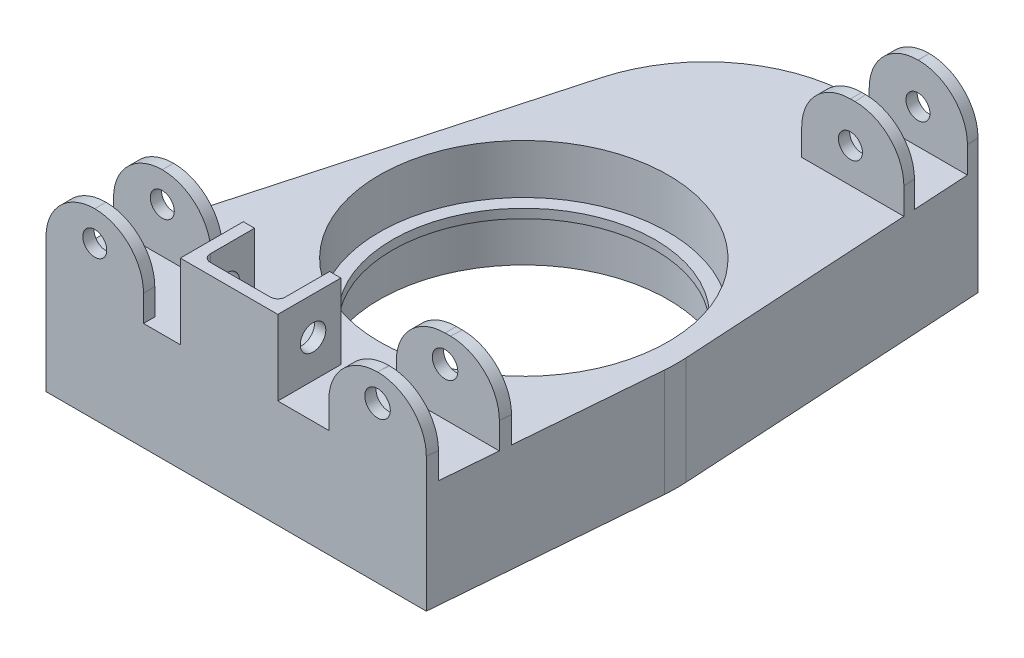
SolidWorks part; units mm, degrees
ref_plane "Front Plane" through (0, 0, 0) normal (0, 0, 1) x (1, 0, 0)
ref_plane "Top Plane" through (0, 0, 0) normal (0, 1, 0) x (1, 0, 0)
ref_plane "Right Plane" through (0, 0, 0) normal (1, 0, 0) x (0, 0, -1)
sketch "Sketch1" plane through (0, 0, 0) normal (0, 1, 0) x (1, 0, 0)
  line L0 (-78.3166, -83.4598) -> (50.4493, -83.4598)
  line L1 (56.8393, -5.2886) -> (50.4493, 103.3395)
  line L2 (50.4493, 103.3395) -> (9.0638, 103.3395)
  line L3 (-39.909, 66.0414) -> (-73.7736, -56.7898)
  line L4 (50.4493, 103.3395) -> (50.4493, -83.4598) construction
  line L5 (50.4493, -83.4598) -> (56.8393, -5.2886)
  line L6 (-78.3166, -83.4598) -> (-78.3166, -56.7898)
  line L7 (-78.3166, -56.7898) -> (-73.7736, -56.7898)
  circle A0 centre (0, 0) radius 48.895
  circle A2 centre (0, 0) radius 120.65
  arc A3 (9.0638, 103.3395) -> (-39.909, 66.0414) centre (9.0638, 52.5395) ccw
  point P10 (0, -48.895)
  point P11 (48.895, 0)
  point P16 (-48.895, 0)
  dimension "D2" = 97.79
  dimension "D3" = 7.62
  dimension "D4" = 8.89
  dimension "D5" = 26.67
  dimension "D1" = 241.3
  dimension "D6" = 50.8
extrude "Base" add sketch "Sketch1" along normal blind 36.5 contours L2 L3 L0 L1 A0 | L1 L4 A0 L5 region at (-76.0109, 0, 70.1248)
sketch "Sketch2" plane through (0, 36.5, 0) normal (0, 1, 0) x (1, 0, 0)
  line L0 (50.4493, 103.3395) -> (50.6734, 99.5295)
  line L1 (56.8393, -5.2886) -> (50.4493, 103.3395) construction
  line L2 (50.6734, 99.5295) -> (17.4293, 99.5295)
  line L3 (17.4293, 99.5295) -> (17.4293, 103.3395)
  line L4 (50.4493, 103.3395) -> (9.0638, 103.3395) construction
  line L5 (17.4293, 103.3395) -> (50.4493, 103.3395)
  line L6 (17.4293, -79.6498) -> (50.7608, -79.6498)
  line L7 (50.7608, -79.6498) -> (50.4493, -83.4598)
  line L8 (-78.3166, -83.4598) -> (50.4493, -83.4598) construction
  line L9 (50.4493, -83.4598) -> (17.4293, -83.4598)
  line L10 (17.4293, -83.4598) -> (17.4293, -79.6498)
  line L11 (17.4293, 103.3395) -> (17.4293, -83.4598) construction
  line L12 (50.4493, -83.4598) -> (56.8393, -5.2886) construction
  line L13 (17.4293, 80.4795) -> (17.4293, 76.6695)
  line L14 (17.4293, 76.6695) -> (52.0182, 76.6695)
  line L15 (52.0182, 76.6695) -> (51.794, 80.4795)
  line L16 (51.794, 80.4795) -> (17.4293, 80.4795)
  line L17 (-78.3166, -83.4598) -> (-78.3166, -56.7898) construction
  line L18 (17.4293, -56.7898) -> (52.6294, -56.7898)
  line L19 (17.4293, -56.7898) -> (17.4293, -60.5998)
  line L20 (17.4293, -60.5998) -> (52.318, -60.5998)
  line L21 (52.6294, -56.7898) -> (52.318, -60.5998)
  line L22 (-45.2966, -56.7898) -> (-78.3166, -56.7898)
  line L23 (-45.2966, -56.7898) -> (-45.2966, -60.5998)
  line L24 (-45.2966, -60.5998) -> (-78.3166, -60.5998)
  line L25 (-78.3166, -56.7898) -> (-78.3166, -60.5998)
  line L26 (-45.2966, -83.4598) -> (-45.2966, -60.0458) construction
  line L27 (-78.3166, -79.6498) -> (-45.2966, -79.6498)
  line L28 (-78.3166, -79.6498) -> (-78.3166, -83.4598)
  line L29 (-78.3166, -83.4598) -> (-45.2966, -83.4598)
  line L30 (-45.2966, -79.6498) -> (-45.2966, -83.4598)
  line L31 (-78.3166, -83.4598) -> (50.4493, -83.4598) construction
  point P40 (-78.3166, -83.4598)
  dimension "D1" = 33.02
  dimension "D2" = 3.81
  dimension "D3" = 3.81
  dimension "D4" = 19.05
  dimension "D5" = 3.81
  dimension "D6" = 3.81
  dimension "D7" = 19.05
  dimension "D8" = 33.02
  dimension "D9" = 3.81
  dimension "D10" = 3.81
extrude "A-Arms" add sketch "Sketch2" along normal blind 25.4
fillet "Fillet a-arm tab f" radius 16.51 12 edges at (50.605, 61.9, 81.5548) (52.4737, 61.9, 58.6948) (17.4293, 61.9, 81.5548) (17.4293, 61.9, 58.6948) (51.9061, 61.9, -78.5745) (50.5614, 61.9, -101.4345) (17.4293, 61.9, -78.5745) (17.4293, 61.9, -101.4345) (-78.3166, 61.9, 81.5548) (-45.2966, 61.9, 81.5548) (-45.2966, 61.9, 58.6948) (-78.3166, 61.9, 58.6948)
fillet "Fillet2" radius 50.8 1 edges at (56.8393, 18.25, 5.2886)
ref_plane "Plane1" through (0, 1, 0) normal (0, -1, 0) x (-1, 0, 0)
sketch "Sketch3" plane through (0, 1, 0) normal (0, -1, 0) x (-1, 0, 0)
  line L0 (43.8545, 51.7309) -> (51.7371, 53.9041)
  line L1 (39.909, 66.0414) -> (73.7736, -56.7898) construction
  line L2 (63.9719, -21.2377) -> (72.1885, -18.9724)
  line L3 (54.0145, 33.5988) -> (63.3923, -0.4157)
  line L4 (43.8545, 51.7309) -> (63.9719, -21.2377)
  circle A0 centre (0, 0) radius 71.12
  circle A1 centre (53.7624, 46.5582) radius 4.191
  circle A2 centre (70.1632, -11.6265) radius 4.191
  arc A3 (56.852, 39.5926) -> (51.7371, 53.9041) centre (53.7624, 46.5582) ccw
  arc A4 (72.1885, -18.9724) -> (69.039, -4.0899) centre (70.1632, -11.6265) ccw
  arc A5 (63.3923, -0.4157) -> (69.039, -4.0899) centre (68.2896, 0.9345) ccw
  arc A6 (54.0145, 33.5988) -> (56.852, 39.5926) centre (58.9118, 34.949) cw
  dimension "D1" = 60.452
  dimension "D2" = 142.24
  dimension "D3" = 8.382
  dimension "D4" = 8.382
  dimension "D5" = 15.24
  dimension "D6" = 15.24
  dimension "D7" = 5.08
extrude "Boss-Extrude3" add sketch "Sketch3" against normal blind 10 contours L3 A6 A3 A0 A1 L0 L4 L2 A2 A4 A5 | A0 A3 L0 A1 | L2 A4 A0 A2 region at (-57.0001, 1, -15.6865) region at (-49.7533, 1, -53.1565) region at (-69.0083, 1, 17.9571)
fillet "Fillet3" radius 12.7 2 edges at (-43.8545, 6, -51.7309) (-63.9719, 6, 21.2377)
sketch "Sketch6" plane through (0, 0, -103.3395) normal (0, 0, -1) x (-1, 0, 0)
  line L0 (-33.9251, 61.9) -> (-33.9251, 40.2979) construction
  circle A1 centre (-33.9251, 48.2) radius 4.064
  dimension "D1" = 13.7
  dimension "D2" = 8.128
extrude "Tab Holes 1" cut sketch "Sketch6" against normal blind 38.1
sketch "Sketch7" plane through (0, 0, 56.7898) normal (0, 0, -1) x (-1, 0, 0)
  line L0 (61.8066, 61.9) -> (61.8066, 41.58) construction
  circle A0 centre (61.8066, 51.74) radius 4.064
  dimension "D1" = 10.16
  dimension "D2" = 8.128
extrude "Tab Holes 2" cut sketch "Sketch7" against normal through all
ref_plane "midplane" through (0, 18.25, 0) normal (0, 1, 0) x (1, 0, 0)
sketch "Sketch8" plane through (0, 18.25, 0) normal (0, 1, 0) x (1, 0, 0)
  circle A0 centre (0, 0) radius 48.895
  circle A1 centre (0, 0) radius 44.45
extrude "mid-feature bearing" add sketch "Sketch8" along normal blind 1.524 and the other way blind 1.524
sketch "Sketch9" plane through (0, 36.5, 0) normal (0, 1, 0) x (1, 0, 0)
  line L0 (-45.2966, -83.4598) -> (17.4293, -83.4598) construction
  line L1 (-32.844, -83.4598) -> (0.176, -83.4598)
  line L2 (-32.844, -83.4598) -> (-32.844, -79.6498)
  line L3 (-32.844, -79.6498) -> (0.176, -79.6498)
  line L4 (0.176, -83.4598) -> (0.176, -79.6498)
  line L6 (0.176, -79.6498) -> (-3.634, -79.6498)
  line L7 (0.176, -79.6498) -> (0.176, -62.1226)
  line L8 (0.176, -62.1226) -> (-3.634, -62.1226)
  line L9 (-3.634, -79.6498) -> (-3.634, -62.1226)
  line L10 (-32.844, -79.6498) -> (-29.034, -79.6498)
  line L11 (-32.844, -79.6498) -> (-32.844, -62.1226)
  line L12 (-32.844, -62.1226) -> (-29.034, -62.1226)
  line L13 (-29.034, -79.6498) -> (-29.034, -62.1226)
  line M30 (-45.2966, -83.4598) -> (17.4293, -83.4598)
  dimension "D1" = 3.81
  dimension "D2" = 3.81
  dimension "D3" = 3.81
  dimension "D4" = 25.4
extrude "Boss-Extrude5" add sketch "Sketch9" along normal blind 25.4 contours L3 L13 L12 L11 | L4 L3 L2 M30 | L9 L3 L7 L8 region at (-16.334, 36.5, 81.5548) region at (-30.939, 36.5, 70.8862) region at (-1.729, 36.5, 70.8862)
fillet "Pushrod Str" radius 2.54 2 edges at (-3.634, 49.2, 79.6498) (-29.034, 49.2, 79.6498)
sketch "Sketch10" plane through (-32.844, 0, 0) normal (-1, 0, 0) x (0, 0, 1)
  line L0 (62.1226, 49.2) -> (80.5175, 49.2) construction
  line L1 (62.1226, 61.9) -> (62.1226, 36.5) construction
  circle A0 centre (71.5365, 49.2) radius 4.318
extrude "Pushrod Holes" cut sketch "Sketch10" against normal through all
mirror "Mirror2" [suppressed] of bodies 108
delete or keep bodies "Body-Delete/Keep 1" [suppressed] type delete bodies bodies 108
sketch "Sketch11" plane through (0, 0, 83.4598) normal (0, 0, -1) x (-1, 0, 0)
  line L0 (-33.9393, 61.9) -> (-33.9393, 36.5) construction
  line L2 (-17.4293, 36.5) -> (-50.4493, 36.5) construction
  line L3 (-50.4493, 45.39) -> (-50.4493, 0) construction
  circle A0 centre (-33.9393, 52.74) radius 4.318
  arc A1 (-17.4293, 45.39) -> (-33.9118, 61.9) centre (-33.9393, 45.39) ccw construction
  point P2 (-33.9393, 36.5)
  point P3 (-33.9118, 61.9)
  dimension "D1" = 9.16
extrude "Tab Holes 3" cut sketch "Sketch11" along normal blind 50.8
